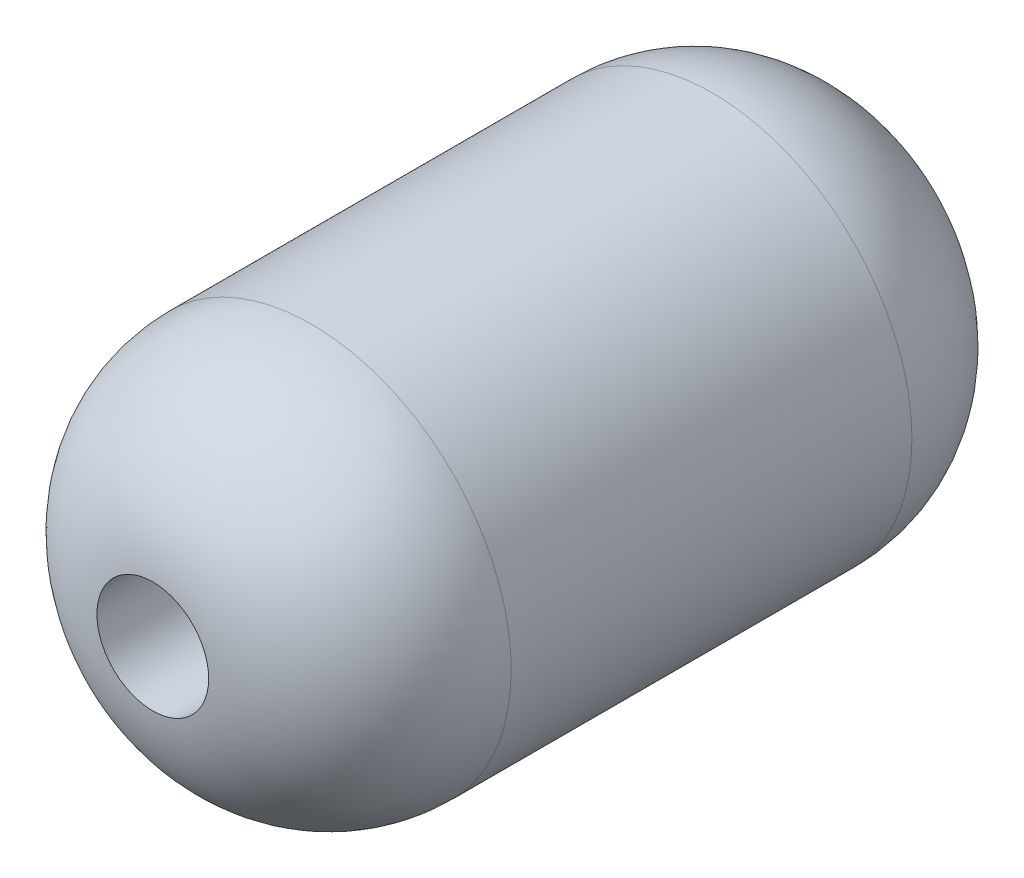
SolidWorks part; units mm, degrees
ref_plane "Front Plane" through (0, 0, 0) normal (0, 0, 1) x (1, 0, 0)
ref_plane "Top Plane" through (0, 0, 0) normal (0, 1, 0) x (1, 0, 0)
ref_plane "Right Plane" through (0, 0, 0) normal (1, 0, 0) x (0, 0, -1)
sketch "Sketch1" plane through (0, 0, 0) normal (0, 0, 1) x (1, 0, 0)
  circle A0 centre (-4.4028, 1.4363) radius 2.5
  circle A1 centre (-4.4028, 1.4363) radius 0.7
  dimension "D1" = 5
  dimension "D2" = 1.4
  dimension "D3" = 0
extrude "Boss-Extrude2" add sketch "Sketch1" along normal blind 9
fillet "Fillet2" radius 2 2 edges at (-1.9028, 1.4363, 0) (-1.9028, 1.4363, 9)
